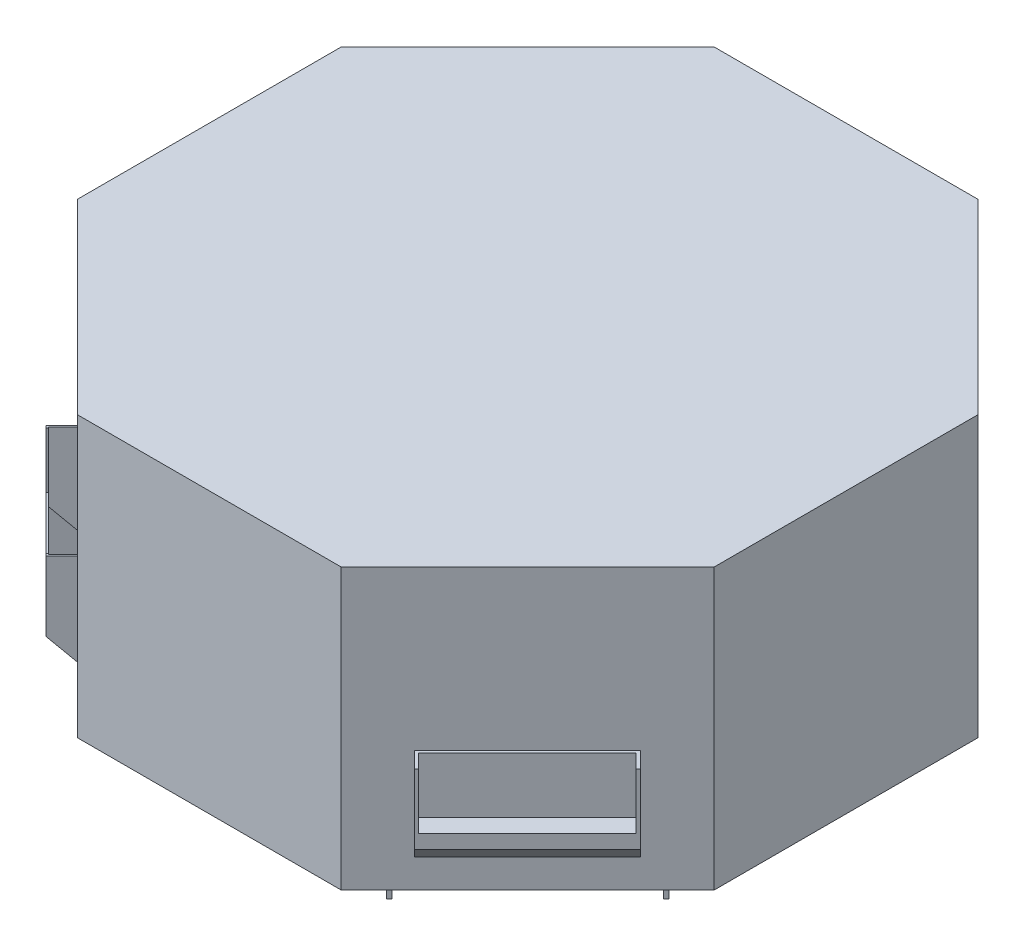
SolidWorks part; units mm, degrees
material "Copper"
ref_plane "Front Plane" through (0, 0, 0) normal (0, 0, 1) x (1, 0, 0)
ref_plane "Top Plane" through (0, 0, 0) normal (0, 1, 0) x (1, 0, 0)
ref_plane "Right Plane" through (0, 0, 0) normal (1, 0, 0) x (0, 0, -1)
sketch "Sketch1" plane through (0, 0, 0) normal (0, 1, 0) x (1, 0, 0)
  line L0 (-209.55, 0) -> (209.55, 0)
  line L1 (209.55, 0) -> (505.8985, 296.3485)
  line L2 (505.8985, 296.3485) -> (505.8985, 715.4485)
  line L3 (505.8985, 715.4485) -> (209.55, 1011.7969)
  line L4 (209.55, 1011.7969) -> (-209.55, 1011.7969)
  line L5 (-209.55, 1011.7969) -> (-505.8985, 715.4485)
  line L6 (-505.8985, 715.4485) -> (-505.8985, 296.3485)
  line L7 (-505.8985, 296.3485) -> (-209.55, 0)
  point P3 (0, 0)
  dimension "D1" = 419.1
  dimension "D2" = 419.1
  dimension "D3" = 135
  dimension "D4" = 419.1
  dimension "D5" = 135
  dimension "D6" = 419.1
  dimension "D7" = 135
  dimension "D8" = 419.1
extrude "Boss-Extrude1" add sketch "Sketch1" along normal blind 444.5
sketch "Sketch2" plane through (-505.8985, 0, 0) normal (-1, 0, 0) x (0, 0, 1)
  line L0 (-715.4485, 444.5) -> (-715.4485, 0) construction
  line L1 (-709.0985, 412.75) -> (-302.6985, 412.75)
  line L2 (-709.0985, 412.75) -> (-709.0985, 6.35)
  line L3 (-709.0985, 6.35) -> (-302.6985, 6.35)
  line L4 (-302.6985, 412.75) -> (-302.6985, 6.35)
  line L5 (-715.4485, 0) -> (-296.3485, 0) construction
  dimension "D1" = 406.4
  dimension "D2" = 406.4
  dimension "D3" = 6.35
  dimension "D4" = 6.35
extrude "Cut-Extrude1" [suppressed] cut sketch "Sketch2" against normal blind 406.4
ref_plane "Plane1" through (0, 0, 0) normal (-1, 0, 0) x (0, 0, 1)
mirror "Mirror1" [suppressed] about plane through (0, 0, 0) normal (-1, 0, 0)
sketch "Sketch3" plane through (0, 0, 0) normal (0, -1, 0) x (1, 0, 0)
  line L0 (-505.8985, -296.3485) -> (-209.55, 0) construction
  line L1 (-211.52, -78.8523) -> (-207.0299, -74.3621)
  line L2 (-211.52, -78.8523) -> (-193.5595, -96.8128)
  line L3 (-193.5595, -96.8128) -> (-189.0694, -92.3226)
  line L4 (-207.0299, -74.3621) -> (-189.0694, -92.3226)
  dimension "D1" = 50.8
  dimension "D2" = 90
  dimension "D3" = 6.35
  dimension "D4" = 25.4
extrude "Boss-Extrude2" add sketch "Sketch3" along normal blind 50.8
sketch "Sketch4" plane through (-145.1862, 0, -145.1862) normal (-0.7071, 0, -0.7071) x (-0.7071, 0, 0.7071)
  line L0 (93.8103, -50.8) -> (68.4103, -50.8) construction
  circle A0 centre (82.3043, -44.45) radius 3.175
  circle A1 centre (81.2451, -6.3647) radius 3.175
  dimension "D1" = 6.35
  dimension "D2" = 6.35
  dimension "D3" = 38.1
  dimension "D4" = 6.35
extrude "Cut-Extrude2" cut sketch "Sketch4" against normal blind 50.8
ref_plane "Plane6" through (-252.9492, 0, -252.9492) normal (-0.7071, 0, -0.7071) x (-0.7071, 0, 0.7071)
mirror "Mirror3" about plane through (-252.9492, 0, -252.9492) normal (-0.7071, 0, -0.7071) of "Cut-Extrude2", "Boss-Extrude2"
mirror "Mirror4" about plane through (0, 0, 0) normal (-1, 0, 0) of "Mirror3", "Cut-Extrude2", "Boss-Extrude2"
sketch "Sketch5" plane through (-252.9492, 0, -252.9492) normal (-0.7071, 0, -0.7071) x (-0.7071, 0, 0.7071)
  line L0 (146.05, 43.5859) -> (183.4122, 80.9481)
  line L1 (183.4122, 80.9481) -> (183.4122, 191.6981)
  line L2 (183.4122, 191.6981) -> (146.05, 191.6981)
  line L3 (146.05, 191.6981) -> (146.05, 43.5859)
extrude "Boss-Extrude3" add sketch "Sketch5" along normal blind 127 and the other way blind 127
shell "Shell1" thickness 2.54 removed face at (-370.1827, 191.6981, -135.7157)
mirror "Mirror5" about plane through (0, 0, 0) normal (-1, 0, 0) of "Boss-Extrude3"
sketch "Sketch6" plane through (0, 191.6981, 0) normal (0, 1, 0) x (1, 0, 0)
  line L0 (305.9606, 26.8233) -> (273.9822, 58.8016)
  line L5 (273.9822, 58.8016) -> (446.7092, 231.5286)
  line L6 (446.7092, 231.5286) -> (478.6875, 199.5503)
  line L7 (478.6875, 199.5503) -> (305.9606, 26.8233)
extrude "Cut-Extrude3" cut sketch "Sketch6" against normal blind 88.9 and the other way blind 7.62
mirror "Mirror2" about plane through (0, 0, 0) normal (-1, 0, 0) of "Cut-Extrude2", "Boss-Extrude2"
mirror "Mirror6" about plane through (0, 0, 0) normal (-1, 0, 0) of "Cut-Extrude3"
